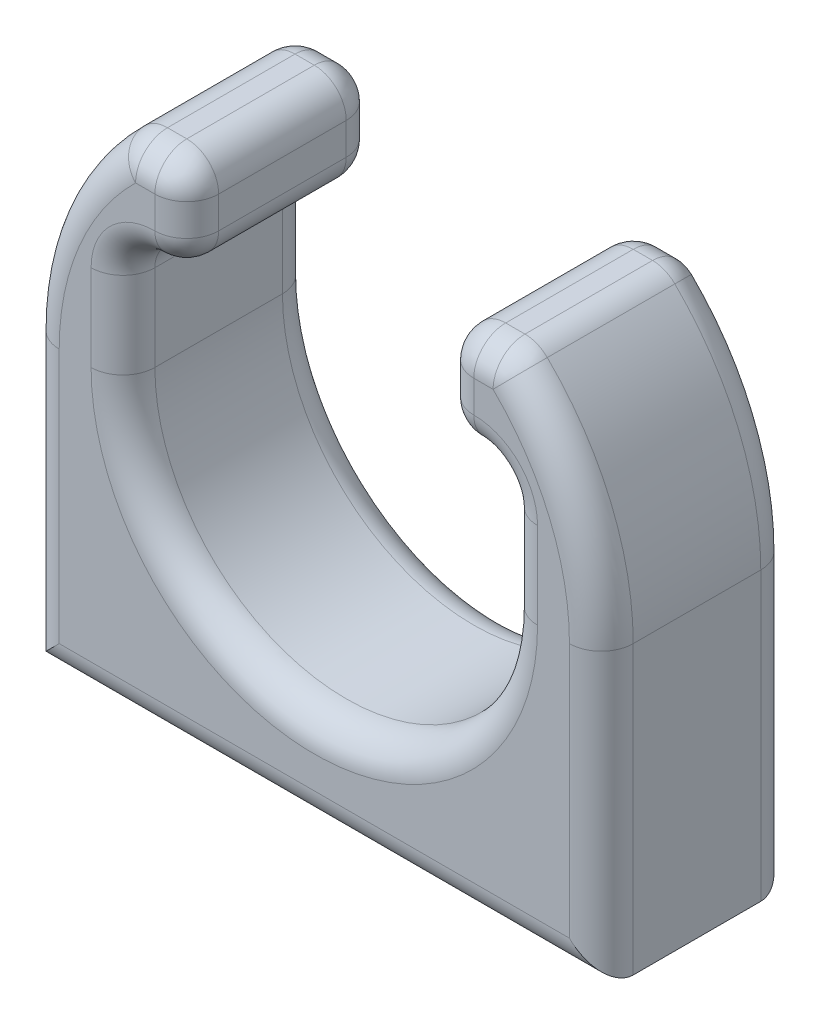
SolidWorks part; units mm, degrees
ref_plane "Спереди" through (0, 0, 0) normal (0, 0, 1) x (1, 0, 0)
ref_plane "Сверху" through (0, 0, 0) normal (0, 1, 0) x (1, 0, 0)
ref_plane "Справа" through (0, 0, 0) normal (1, 0, 0) x (0, 0, -1)
sketch "Эскиз1" plane through (0, 0, 0) normal (0, 0, 1) x (1, 0, 0)
  line L0 (-3, 0) -> (-3, 1.8541)
  line L1 (3, 0) -> (3, 1.8541)
  line L2 (-4.5, 0) -> (-4.5, -4.5)
  line L3 (-4.5, -4.5) -> (4.5, -4.5)
  line L4 (4.5, -4.5) -> (4.5, 0)
  line L6 (-3, 3.3541) -> (-2, 3.3541)
  line L8 (-3, 1.8541) -> (-2, 1.8541)
  line L9 (-2, 3.3541) -> (-2, 1.8541)
  line L10 (3, 3.3541) -> (2, 3.3541)
  line L12 (3, 1.8541) -> (2, 1.8541)
  line L13 (2, 3.3541) -> (2, 1.8541)
  arc A0 (-3, 3.3541) -> (-4.5, 0) centre (0, 0) ccw
  arc A1 (-3, 0) -> (3, 0) centre (0, 0) ccw
  arc A2 (4.5, 0) -> (3, 3.3541) centre (0, 0) ccw
  dimension "D1" = 6
  dimension "D2" = 9
  dimension "D3" = 1.5
  dimension "D4" = 1
  dimension "D5" = 1
  dimension "D6" = 1.5
  dimension "D7" = 6
  dimension "D8" = 4
extrude "Бобышка-Вытянуть1" add sketch "Эскиз1" along normal blind 3
fillet "Скругление1" radius 0.5 32 edges at (3, 3.3541, 1.5) (-4.5, -2.25, 0) (0, -4.5, 0) (4.5, -2.25, 0) (4.1079, 1.8371, 0) (2.5, 3.3541, 0) (0, -3, 0) (-3, 0.9271, 0) (-2, 2.6041, 0) (-2.5, 3.3541, 0) (-4.1079, 1.8371, 0) (3, 1.8541, 1.5) (3, 0.9271, 0) (-2.5, 3.3541, 3) (-2, 2.6041, 3) (-3, 0.9271, 3) (0, -3, 3) (3, 0.9271, 3) (2.5, 3.3541, 3) (4.1079, 1.8371, 3) (4.5, -2.25, 3) (0, -4.5, 3) (-4.5, -2.25, 3) (-4.1079, 1.8371, 3) (2, 3.3541, 1.5) (2, 2.6041, 3) (2, 1.8541, 1.5) (2, 2.6041, 0) (-3, 3.3541, 1.5) (-2, 3.3541, 1.5) (-3, 1.8541, 1.5) (-2, 1.8541, 1.5)
